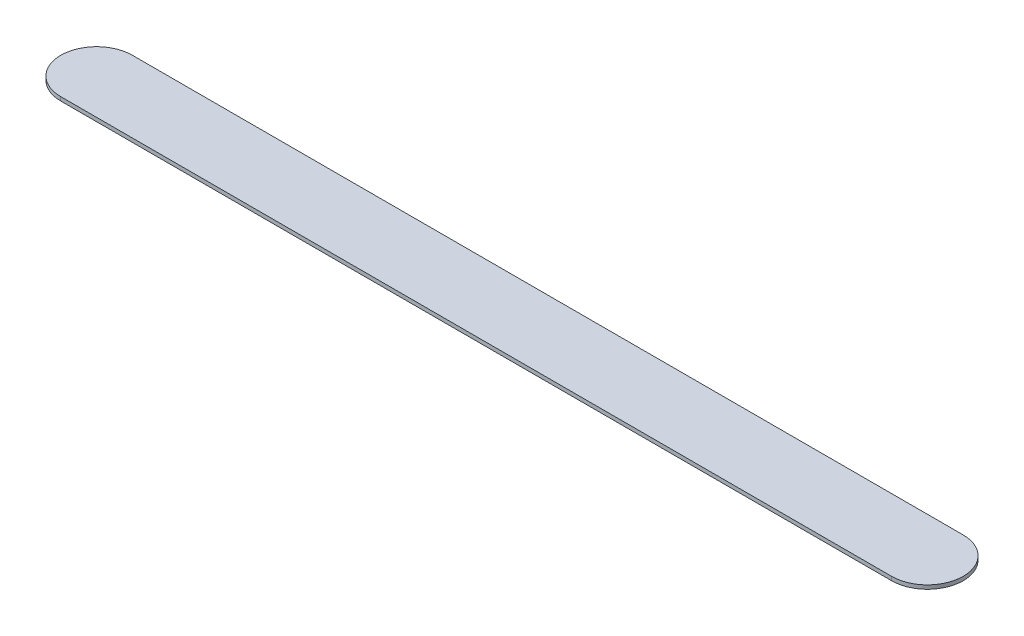
SolidWorks part; units mm, degrees
ref_plane "Front Plane" through (0, 0, 0) normal (0, 0, 1) x (1, 0, 0)
ref_plane "Top Plane" through (0, 0, 0) normal (0, 1, 0) x (1, 0, 0)
ref_plane "Right Plane" through (0, 0, 0) normal (1, 0, 0) x (0, 0, -1)
sketch "Sketch1" plane through (0, 0, 0) normal (0, 1, 0) x (1, 0, 0)
  line L0 (0, 0) -> (160, 0) construction
  line L1 (0, 6.9) -> (160, 6.9)
  line L2 (0, -6.9) -> (160, -6.9)
  arc A0 (0, 6.9) -> (0, -6.9) centre (0, 0) ccw
  arc A1 (160, -6.9) -> (160, 6.9) centre (160, 0) ccw
  point P3 (80, 0)
  dimension "D1" = 13.8
  dimension "D2" = 160
base flange "Base-Flange1" sketch "Sketch1" thickness 0.7366 reverse thickness direction no parameters "D1"=0.7366
sketch "Bend-Lines1" plane through (0, 0, 0) normal (0, 1, 0) x (1, 0, 0)
sketch "Bounding-Box1" plane through (0, 0, 0) normal (0, 1, 0) x (1, 0, 0)
sheet metal parameters "Sheet-Metal1" thickness 0.7366 parameters "D1"=0.7366
flat pattern "Flat-Pattern1" [suppressed]
sketch "Bend-Lines2" plane through (0, 0, 0) normal (0, 1, 0) x (1, 0, 0)
sketch "Bounding-Box2" [suppressed] plane through (0, 0, 0) normal (0, 1, 0) x (1, 0, 0)
